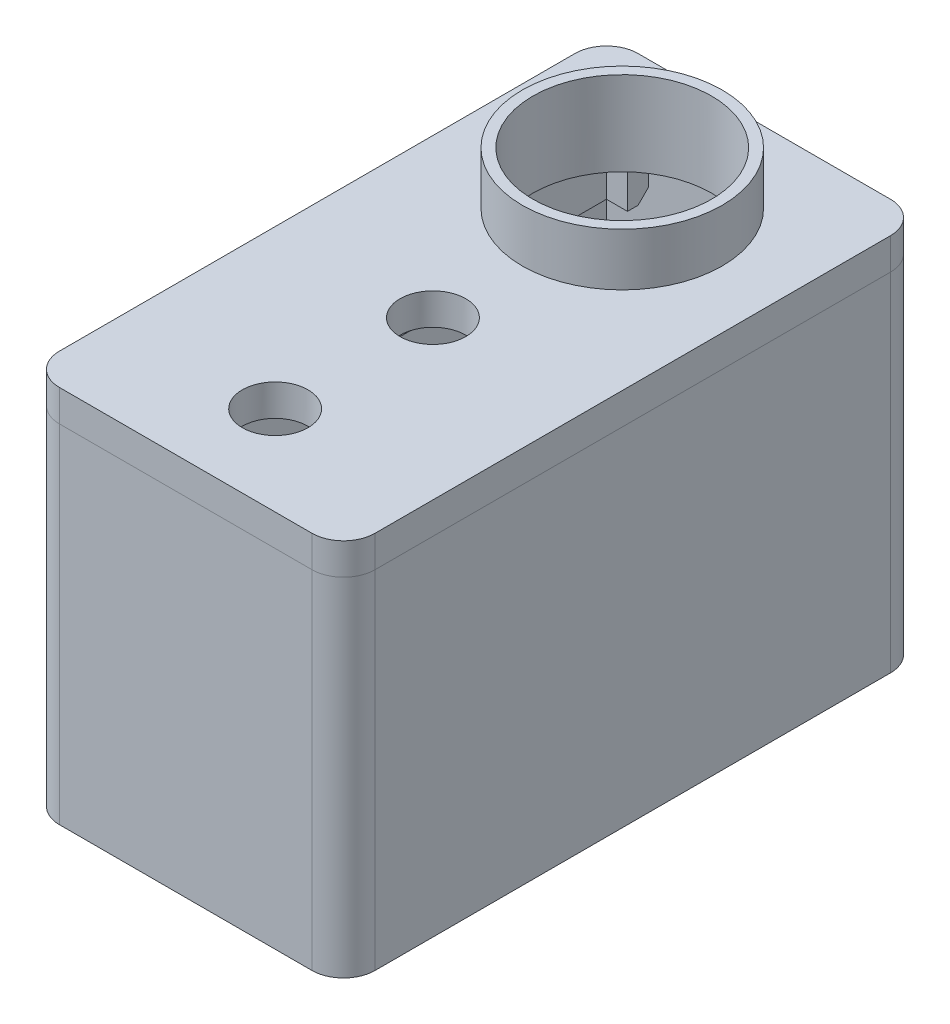
SolidWorks part; units mm, degrees
ref_plane "Front Plane" through (0, 0, 0) normal (0, 0, 1) x (1, 0, 0)
ref_plane "Top Plane" through (0, 0, 0) normal (0, 1, 0) x (1, 0, 0)
ref_plane "Right Plane" through (0, 0, 0) normal (1, 0, 0) x (0, 0, -1)
sketch "Sketch1" plane through (0, 0, 0) normal (0, 1, 0) x (1, 0, 0)
  line L1 (-15, -27.5) -> (15, -27.5)
  line L2 (-15, -27.5) -> (-15, 27.5)
  line L3 (-15, 27.5) -> (15, 27.5)
  line L4 (15, -27.5) -> (15, 27.5)
  line L5 (-15, -27.5) -> (15, 27.5) construction
  line L6 (-15, 27.5) -> (15, -27.5) construction
  point P0 (0, 0)
  dimension "D1" = 55
  dimension "D2" = 30
extrude "Boss-Extrude7" add sketch "Sketch1" against normal blind 3
sketch "Sketch14" plane through (0, -3, 0) normal (0, -1, 0) x (1, 0, 0)
  line L0 (12, -24.5) -> (12, 24.5)
  line L1 (12, 24.5) -> (-12, 24.5)
  line L2 (-12, 24.5) -> (-12, -24.5)
  line L3 (-12, -24.5) -> (12, -24.5)
  line L4 (15, -27.5) -> (15, 27.5)
  line L5 (15, 27.5) -> (-15, 27.5)
  line L6 (-15, 27.5) -> (-15, -27.5)
  line L7 (-15, -27.5) -> (15, -27.5)
  line L8 (15, -27.5) -> (15, 27.5)
  line L9 (15, 27.5) -> (-15, 27.5)
  line L10 (-15, 27.5) -> (-15, -27.5)
  line L11 (-15, -27.5) -> (15, -27.5)
  dimension "D1" = 0
  dimension "D2" = 3
extrude "Boss-Extrude8" add sketch "Sketch14" along normal blind 33 separate body
sketch "Sketch17" plane through (-12.5, 0, -27.5) normal (0, 0, -1) x (-1, 0, 0)
  line L0 (-17.5, -36) -> (-17.5, -33)
  line L2 (-7.5, -33) -> (-7.5, -36)
  line L3 (-7.5, -36) -> (-17.5, -36)
  line L4 (-27.5, -36) -> (2.5, -36) construction
  arc A0 (-17.5, -33) -> (-7.5, -33) centre (-12.5, -33) cw
  point P6 (-12.5, -36)
  dimension "D1" = 10
  dimension "D2" = 3
extrude "Cut-Extrude1" cut sketch "Sketch17" against normal up to next (3 mm away)
sketch "Sketch23" [suppressed] plane through (0, -36, 0) normal (0, -1, 0) x (1, 0, 0)
  line L2 (-23, 7.5) -> (-15, 7.5) construction
  line L3 (-23, 22.5) -> (-23, 27.5) construction
  line L4 (15, 27.5) -> (-15, 27.5) construction
  line L5 (-15, 27.5) -> (-15, -27.5) construction
  line L7 (189.8967, 22.5) -> (189.8967, -7.5) construction
  line L8 (-23, -7.5) -> (-23, 22.5)
  dimension "D1" = 8
  dimension "D2" = 5
sketch "Sketch24" [suppressed] plane through (0, -36, 0) normal (0, -1, 0) x (1, 0, 0)
  line L0 (-15, 27.5) -> (-23, 27.5)
  line L1 (-15, 27.5) -> (-15, -27.5) construction
  line L2 (-28, 22.5) -> (-28, -7.5)
  line L3 (-23, -12.5) -> (-15, -12.5)
  line L4 (-15, -12.5) -> (-15, 27.5)
  line L5 (15, 27.5) -> (-15, 27.5) construction
  arc A0 (-23, 27.5) -> (-28, 22.5) centre (-23, 22.5) ccw
  arc A1 (-28, -7.5) -> (-23, -12.5) centre (-23, -7.5) ccw
extrude "Boss-Extrude11" [suppressed] add sketch "Sketch24" against normal blind 3
hole_wizard "#8 Clearance Hole2" [suppressed] positions "Sketch25" profile "Sketch26" hole size "#8" standard "ANSI Inch"
sketch "Sketch25" [suppressed] plane through (0, -33, 0) normal (0, 1, 0) x (1, 0, 0)
  point P0 (-23, 7.5)
  point P3 (-23, -22.5)
sketch "Sketch26" plane through (-23, -33, -7.5) normal (1, 0, 0) x (0, 0, 1)
  line L0 (0, 0) -> (0, 3)
  line L1 (0, 3) -> (2.2479, 3)
  line L2 (2.2479, 3) -> (2.2479, 0)
  line L5 (2.2479, 0) -> (0, 0)
  line L11 (0, -6.35) -> (0, 107.95) construction
  dimension "Thru Hole Dia." = 4.4958
  dimension "Thru Hole Depth" = 3
sketch "Sketch27" plane through (0, -36, 0) normal (0, -1, 0) x (1, 0, 0)
  line L0 (-7, -19.5) -> (-7, 5.5) construction
  line L1 (-7, 5.5) -> (-7, -19.5)
  line L2 (-12, -24.5) -> (-5, -24.5) construction
  line L4 (-12, 24.5) -> (-12, -24.5) construction
  circle A0 centre (-7, 5.5) radius 5
  circle A1 centre (-7, -19.5) radius 5
  dimension "D1" = 10
sketch "Sketch29" plane through (0, -36, 0) normal (0, -1, 0) x (1, 0, 0)
  line L0 (-12, 10.5) -> (-7, 10.5)
  line L1 (-12, 24.5) -> (-12, -24.5) construction
  line L2 (-2, 5.5) -> (-2, -24.5)
  line L3 (-12, -24.5) -> (-5, -24.5) construction
  line L4 (-2, -24.5) -> (-12, -24.5)
  line L5 (-12, -24.5) -> (-12, 10.5)
  arc A0 (-7, 10.5) -> (-2, 5.5) centre (-7, 5.5) cw
  circle A1 centre (-7, 5.5) radius 5 construction
extrude "Boss-Extrude12" add sketch "Sketch29" against normal blind 3
hole_wizard "#8 Clearance Hole3" positions "Sketch30" profile "Sketch31" hole size "#8" standard "ANSI Inch" end condition through all
sketch "Sketch30" plane through (0, -33, 0) normal (0, 1, 0) x (1, 0, 0)
  point P0 (-7, -5.5)
  point P2 (-7, 19.5)
sketch "Sketch31" plane through (-7, -33, 5.5) normal (1, 0, 0) x (0, 0, 1)
  line L0 (0, 0) -> (0, 3)
  line L1 (0, 3) -> (2.2479, 3)
  line L2 (2.2479, 3) -> (2.2479, 0)
  line L5 (2.2479, 0) -> (0, 0)
  line L11 (0, -6.35) -> (0, 107.95) construction
  dimension "Thru Hole Dia." = 4.4958
  dimension "Thru Hole Depth" = 3
fillet "Fillet1" radius 3 1 edges at (-2, -34.5, -24.5)
fillet "Fillet2" radius 3 4 edges at (-15, -19.5, 27.5) (-15, -19.5, -27.5) (15, -19.5, -27.5) (15, -19.5, 27.5)
fillet "Fillet3" radius 3 4 edges at (-15, -1.5, 27.5) (-15, -1.5, -27.5) (15, -1.5, -27.5) (15, -1.5, 27.5)
sketch "Sketch35" plane through (0, 0, 0) normal (0, 0, 1) x (1, 0, 0)
  line L0 (-12, -3) -> (12, -3) construction
  line L1 (10.25, -3) -> (11.75, -3)
  line L2 (10.25, -3) -> (10.25, -10.25)
  line L3 (10.25, -10.25) -> (11.75, -10.25)
  line L4 (11.75, -3) -> (11.75, -8)
  line L5 (12, -36) -> (12, -3) construction
  line L6 (11.75, -8) -> (12.5, -8)
  line L7 (12.5, -8) -> (12.5, -9.5)
  line L8 (12.5, -9.5) -> (11.75, -10.25)
  line L9 (0, 0) -> (0, -8.402) construction
  line L10 (-12.5, -9.5) -> (-11.75, -10.25)
  line L11 (-12.5, -8) -> (-12.5, -9.5)
  line L12 (-11.75, -8) -> (-12.5, -8)
  line L13 (-11.75, -3) -> (-11.75, -8)
  line L14 (-10.25, -10.25) -> (-11.75, -10.25)
  line L15 (-10.25, -3) -> (-10.25, -10.25)
  line L16 (-10.25, -3) -> (-11.75, -3)
  dimension "D1" = 1.5
  dimension "D2" = 0.25
  dimension "D3" = 0.75
  dimension "D4" = 135
  dimension "D5" = 1.5
  dimension "D6" = 5
extrude "Boss-Extrude13" add sketch "Sketch35" along normal mid plane 10
sketch "Sketch36" plane through (0, 0, 0) normal (0, 0, 1) x (1, 0, 0)
  line L0 (12.5, -9.5) -> (11.75, -10.25) construction
  line L1 (12.5, -8) -> (12.5, -9.5) construction
  line L2 (11.75, -8) -> (12.5, -8) construction
  line L3 (12.5, -9.5) -> (11.75, -10.25) construction
  line L4 (12.5, -8) -> (12.5, -9.5) construction
  line L5 (11.75, -8) -> (12.5, -8) construction
  line L6 (11.75, -8) -> (11.75, -10.25) construction
  line L7 (0, 0) -> (0, -10.1145) construction
  line L8 (11.75, -7.6) -> (12.5, -7.6)
  line L9 (11.75, -7.6) -> (11.75, -11)
  line L10 (11.75, -11) -> (12.5, -11)
  line L11 (12.5, -7.6) -> (12.5, -11)
  line L12 (-11.75, -7.6) -> (-12.5, -7.6)
  line L13 (-12.5, -7.6) -> (-12.5, -11)
  line L14 (-11.75, -11) -> (-12.5, -11)
  line L15 (-11.75, -7.6) -> (-11.75, -11)
  dimension "D1" = 0.4
  dimension "D2" = 0.75
extrude "Cut-Extrude2" cut sketch "Sketch36" against normal mid plane 12
sketch "Sketch37" plane through (0, 0, 0) normal (0, 1, 0) x (1, 0, 0)
  line L0 (0, 6) -> (0, 5) construction
  circle A0 centre (0, -4) radius 3.125
  circle A1 centre (0, -19) radius 3.125
  circle A2 centre (0, -19) radius 6 construction
  circle A3 centre (0, -4) radius 6 construction
  circle A4 centre (0, 14) radius 8.5
  circle A6 centre (0, 14) radius 9 construction
  circle A7 centre (0, 14) radius 9 construction
  circle A8 centre (0, 14) radius 8 construction
  circle A9 centre (0, 14) radius 8 construction
  point P17 (0, 5.5)
  dimension "D1" = 6.25
extrude "Cut-Extrude3" cut sketch "Sketch37" against normal up to next (3 mm away)
sketch "Sketch38" plane through (0, 0, 0) normal (0, 1, 0) x (1, 0, 0)
  circle A0 centre (0, 14) radius 8.5 construction
  circle A1 centre (0, 14) radius 8.5
  circle A4 centre (0, 14) radius 9.5
  circle A5 centre (0, 14) radius 9.5
  dimension "D1" = 1
extrude "Boss-Extrude14" add sketch "Sketch38" along normal up to surface (5 mm away)
sketch "Sketch39" plane through (0, -3, 0) normal (0, -1, 0) x (1, 0, 0)
  line L1 (12, -24.5) -> (12, 24.5) construction
  line L2 (-12, 24.5) -> (-12, -24.5) construction
  line L5 (12, -24.5) -> (12, 24.5) construction
  line L6 (-12, 24.5) -> (-12, -24.5) construction
  line L8 (11.5, 24) -> (7.5, 24)
  line L9 (-11.5, 24) -> (-11.5, -24)
  line L10 (-11.5, -24) -> (-7.5, -24)
  line L11 (11.5, -24) -> (11.5, 24)
  line L12 (9.5, 22) -> (7.5, 22)
  line L13 (-9.5, 22) -> (-9.5, -22)
  line L14 (-9.5, -22) -> (-7.5, -22)
  line L15 (9.5, -22) -> (9.5, 22)
  line L16 (-7.5, -24) -> (-7.5, -22)
  line L17 (7.5, -24) -> (7.5, -22)
  line L18 (7.5, -24) -> (11.5, -24)
  line L19 (-12, -24.5) -> (12, -24.5) construction
  line L20 (-11.5, -24) -> (11.5, -24) construction
  line L21 (7.5, -22) -> (9.5, -22)
  line L22 (-9.5, -22) -> (9.5, -22) construction
  line L23 (-7.5, 22) -> (-7.5, 24)
  line L24 (7.5, 22) -> (7.5, 24)
  line L25 (-7.5, 22) -> (-9.5, 22)
  line L26 (9.5, 22) -> (-9.5, 22) construction
  line L27 (-7.5, 24) -> (-11.5, 24)
  line L28 (11.5, 24) -> (-11.5, 24) construction
  line L29 (12, 24.5) -> (-12, 24.5) construction
  dimension "D1" = 0.5
  dimension "D3" = 2
  dimension "D2" = 2
extrude "Boss-Extrude15" add sketch "Sketch39" along normal blind 5
chamfer "Chamfer1" distance 1 angle 45 8 edges at (9.5, -8, -24) (11.5, -8, -14.5) (11.5, -8, 14.5) (9.5, -8, 24) (-9.5, -8, 24) (-11.5, -8, 14.5) (-11.5, -8, -14.5) (-9.5, -8, -24)
sketch "Sketch41" plane through (0, -36, 0) normal (0, -1, 0) x (1, 0, 0)
  line L0 (-2, -21.5) -> (-2, 5.5) construction
  line L1 (-7, 10.5) -> (-12, 10.5) construction
  line L2 (12, -24.5) -> (12, 24.5) construction
  line L3 (12, 24.5) -> (-12, 24.5) construction
  line L4 (-12, 24.5) -> (-12, 10.5) construction
  line L5 (-2, -5.5) -> (-2, 5.5)
  line L6 (-7, 10.5) -> (-12, 10.5)
  line L7 (12, -5.5) -> (12, 24.5)
  line L8 (12, 24.5) -> (-12, 24.5)
  line L9 (-12, 24.5) -> (-12, 10.5)
  line L10 (-2, -5.5) -> (12, -5.5)
  arc A0 (-2, 5.5) -> (-7, 10.5) centre (-7, 5.5) ccw construction
  arc A1 (-2, 5.5) -> (-7, 10.5) centre (-7, 5.5) ccw
  dimension "D1" = 30
extrude "Boss-Extrude16" add sketch "Sketch41" against normal up to surface (3 mm away) up to face at (-7, -33, 7.7479)
fillet "Fillet4" radius 3 2 edges at (-2, -34.5, -5.5) (12, -34.5, -5.5)
